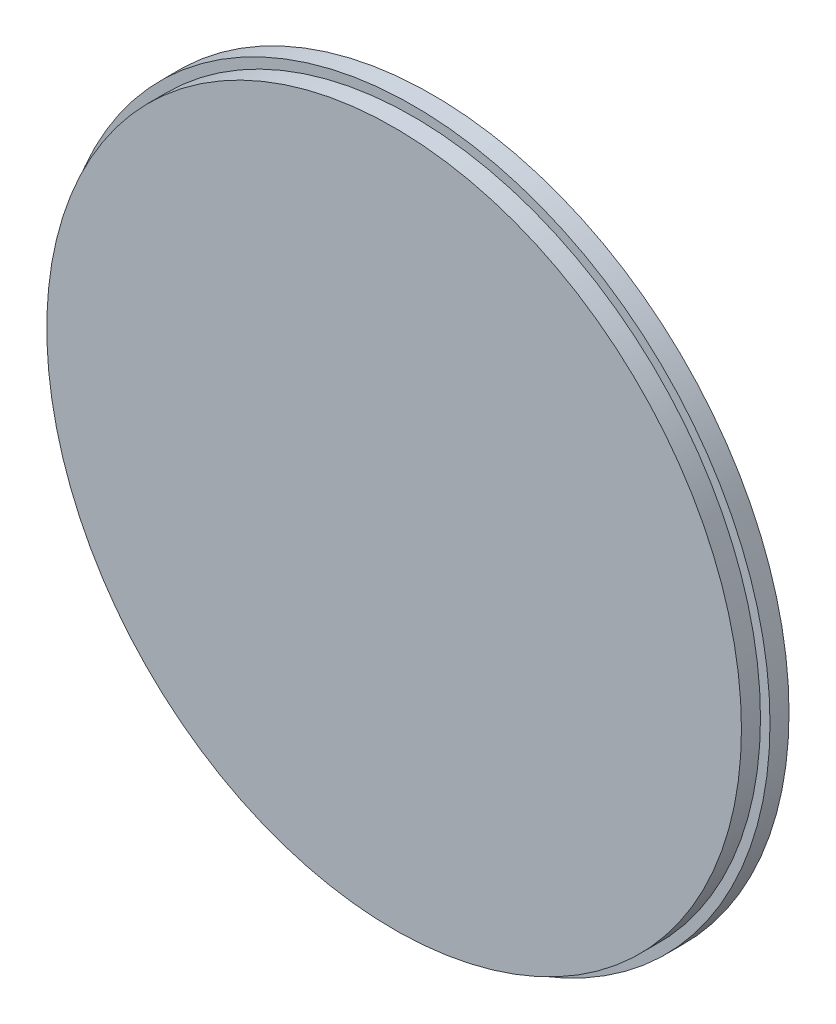
SolidWorks part; units mm, degrees
ref_plane "Front Plane" through (0, 0, 0) normal (0, 0, 1) x (1, 0, 0)
ref_plane "Top Plane" through (0, 0, 0) normal (0, 1, 0) x (1, 0, 0)
ref_plane "Right Plane" through (0, 0, 0) normal (1, 0, 0) x (0, 0, -1)
sketch "Sketch1" plane through (0, 0, 0) normal (0, 0, 1) x (1, 0, 0)
  circle A0 centre (0, 0) radius 18.75
  circle A1 centre (0, 0) radius 18.25
  dimension "D1" = 37.5
  dimension "D2" = 36.5
extrude "Boss-Extrude1" add sketch "Sketch1" along normal blind 1 contours A1 | A0 A1 region at (-18.697, 0, 0) region at (0, 0, 0)
extrude "Boss-Extrude2" add sketch "Sketch1<3>" along normal blind 2 contours A1 region at (0, 0, 0)
sketch "Sketch1<3>" plane through (0, 0, 0) normal (0, 0, 1) x (1, 0, 0) same geometry as "Sketch1"
